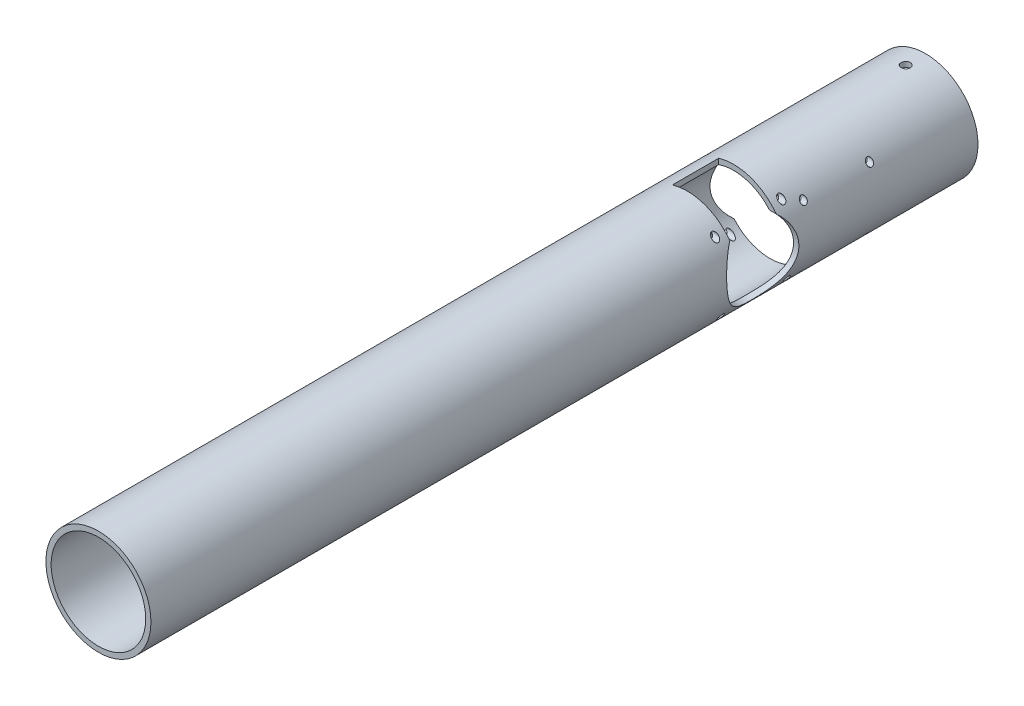
SolidWorks part; units mm, degrees
ref_plane "Front Plane" through (0, 0, 0) normal (0, 0, 1) x (1, 0, 0)
ref_plane "Top Plane" through (0, 0, 0) normal (0, 1, 0) x (1, 0, 0)
ref_plane "Right Plane" through (0, 0, 0) normal (1, 0, 0) x (0, 0, -1)
sketch "Sketch1" plane through (0, 0, 0) normal (0, 0, 1) x (1, 0, 0)
  circle A0 centre (0, 0) radius 31.75
  circle A1 centre (0, 0) radius 28.575
  dimension "D1" = 63.5
  dimension "D2" = 57.15
extrude "Boss-Extrude1" add sketch "Sketch1" along normal blind 250 and the other way blind 250 contours A1 | A0 region at (0, 0, 0)
sketch "Sketch2" plane through (0, 0, 0) normal (1, 0, 0) x (0, 0, -1)
  circle A2 centre (170, -2) radius 21.75
  dimension "D1" = 43.5
  dimension "D2" = 170
  dimension "D3" = 2
extrude "Cut-Extrude1" cut sketch "Sketch2" against normal through all
sketch "Sketch3" plane through (0, 0, 0) normal (1, 0, 0) x (0, 0, -1)
  circle A1 centre (120, 2) radius 21.75
  dimension "D1" = 120
  dimension "D2" = 43.5
  dimension "D3" = 2
extrude "Cut-Extrude2" cut sketch "Sketch3" along normal through all
sketch "Sketch5" plane through (0, 0, 0) normal (1, 0, 0) x (0, 0, -1)
  line L1 (184, -12.75) -> (156, -12.75)
  line L2 (184, -12.75) -> (184, -34.75)
  line L3 (184, -34.75) -> (156, -34.75)
  line L4 (156, -12.75) -> (156, -34.75)
  line L5 (184, -12.75) -> (156, -34.75) construction
  line L6 (184, -34.75) -> (156, -12.75) construction
  circle A0 centre (170, -2) radius 21.75 construction
  circle A1 centre (170, -2) radius 21.75 construction
  point P0 (170, -23.75)
  dimension "D1" = 28
  dimension "D2" = 22
  dimension "D3" = 170
extrude "Cut-Extrude4" cut sketch "Sketch5" against normal through all from offset 9
sketch "Sketch6" plane through (0, 0, 0) normal (1, 0, 0) x (0, 0, -1)
  line L1 (106, 34.75) -> (134, 34.75)
  line L2 (106, 34.75) -> (106, 12.75)
  line L3 (106, 12.75) -> (134, 12.75)
  line L4 (134, 34.75) -> (134, 12.75)
  line L5 (106, 34.75) -> (134, 12.75) construction
  line L6 (106, 12.75) -> (134, 34.75) construction
  circle A0 centre (120, 2) radius 21.75 construction
  circle A1 centre (120, 2) radius 21.75 construction
  point P0 (120, 23.75)
  dimension "D1" = 28
  dimension "D2" = 22
  dimension "D3" = 120
extrude "Cut-Extrude5" cut sketch "Sketch6" along normal through all from offset 9 offset against normal yes
sketch "Sketch8" plane through (0, 0, 0) normal (1, 0, 0) x (0, 0, -1)
  line L1 (80, 42) -> (160, 42)
  line L2 (80, 42) -> (80, -38)
  line L3 (80, -38) -> (160, -38)
  line L4 (160, 42) -> (160, -38)
  line L5 (80, 42) -> (160, -38) construction
  line L6 (80, -38) -> (160, 42) construction
  point P0 (120, 2)
  dimension "D1" = 80
  dimension "D2" = 80
sketch "Sketch9" plane through (0, 0, 0) normal (1, 0, 0) x (0, 0, -1)
  line L0 (80, 42) -> (160, -38) construction
  line L1 (80, -38) -> (160, 42) construction
  circle A0 centre (100, 22) radius 2
  circle A1 centre (140, 22) radius 2
  circle A2 centre (140, -18) radius 2
  circle A3 centre (100, -18) radius 2
  dimension "D2" = 4
  dimension "D4" = 4
  dimension "D6" = 4
  dimension "D8" = 4
  dimension "D1" = 20
  dimension "D3" = 20
  dimension "D5" = 20
  dimension "D7" = 20
extrude "Cut-Extrude7" cut sketch "Sketch9" against normal through all both and the other way through all
sketch "Sketch10" plane through (0, 0, 0) normal (1, 0, 0) x (0, 0, -1)
  line L1 (210, 38) -> (130, 38)
  line L2 (210, 38) -> (210, -42)
  line L3 (210, -42) -> (130, -42)
  line L4 (130, 38) -> (130, -42)
  line L5 (210, 38) -> (130, -42) construction
  line L6 (210, -42) -> (130, 38) construction
  point P0 (170, -2)
  dimension "D1" = 80
  dimension "D2" = 80
sketch "Sketch11" plane through (0, 0, 0) normal (1, 0, 0) x (0, 0, -1)
  line L0 (210, 38) -> (130, -42) construction
  line L1 (210, -42) -> (130, 38) construction
  circle A0 centre (190, 18) radius 2
  circle A1 centre (150, 18) radius 2
  circle A2 centre (150, -22) radius 2
  circle A3 centre (190, -22) radius 2
  dimension "D5" = 4
  dimension "D6" = 4
  dimension "D7" = 4
  dimension "D8" = 4
  dimension "D1" = 20
  dimension "D2" = 20
  dimension "D3" = 20
  dimension "D4" = 20
extrude "Cut-Extrude8" cut sketch "Sketch11" against normal through all both and the other way through all
ref_plane "Plane1" through (0, 31.75, 0) normal (0, 1, 0) x (1, 0, 0)
sketch "Sketch12" plane through (0, 31.75, 0) normal (0, 1, 0) x (1, 0, 0)
  line L0 (31.75, 250) -> (-31.75, 250) construction
  circle A0 centre (0, 238) radius 2.75
  dimension "D2" = 5.5
  dimension "D1" = 12
extrude "Cut-Extrude9" cut sketch "Sketch12" against normal through all
